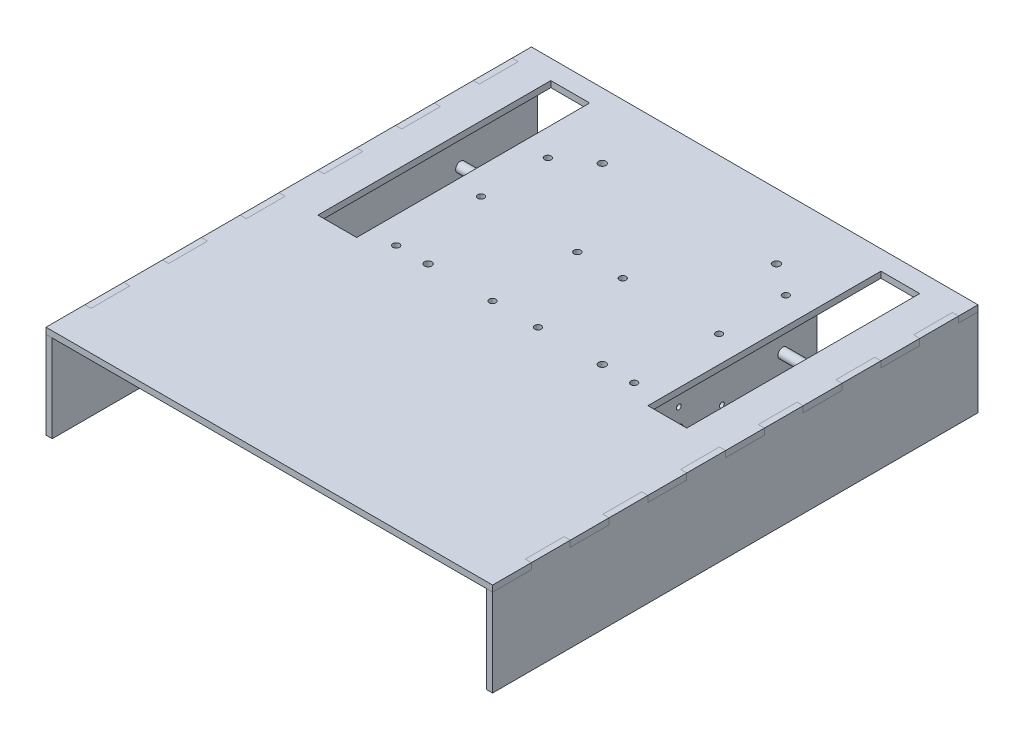
SolidWorks part; units mm, degrees
ref_plane "Front Plane" through (0, 0, 0) normal (0, 0, 1) x (1, 0, 0)
ref_plane "Top Plane" through (0, 0, 0) normal (0, 1, 0) x (1, 0, 0)
ref_plane "Right Plane" through (0, 0, 0) normal (1, 0, 0) x (0, 0, -1)
sketch "Sketch2" plane through (0, 0, 0) normal (0, 1, 0) x (1, 0, 0)
  line L7 (-172.2662, -88.2141) -> (57.7338, -88.2141)
  line L8 (17.7338, 151.7859) -> (37.7338, 151.7859)
  line L9 (57.7338, -88.2141) -> (57.7338, -68.2141)
  line L10 (57.7338, -68.2141) -> (54.5588, -68.2141)
  line L11 (54.5588, -68.2141) -> (54.5588, -48.2141)
  line L12 (54.5588, -48.2141) -> (57.7338, -48.2141)
  line L13 (-172.2662, -88.2141) -> (-172.2662, -68.2141)
  line L14 (-172.2662, -68.2141) -> (-169.0912, -68.2141)
  line L15 (-169.0912, -68.2141) -> (-169.0912, -48.2141)
  line L16 (-169.0912, -48.2141) -> (-172.2662, -48.2141)
  line L17 (-172.2662, -48.2141) -> (-172.2662, -28.2141)
  line L18 (-172.2662, -28.2141) -> (-169.0912, -28.2141)
  line L19 (-169.0912, -28.2141) -> (-169.0912, -8.2141)
  line L20 (-169.0912, -8.2141) -> (-172.2662, -8.2141)
  line L21 (57.7338, -28.2141) -> (54.5588, -28.2141)
  line L22 (54.5588, -28.2141) -> (54.5588, -8.2141)
  line L23 (54.5588, -8.2141) -> (57.7338, -8.2141)
  line L24 (57.7338, -48.2141) -> (57.7338, -28.2141)
  line L25 (-172.2662, -8.2141) -> (-172.2662, 11.7859)
  line L26 (-172.2662, 11.7859) -> (-169.0912, 11.7859)
  line L27 (-169.0912, 11.7859) -> (-169.0912, 31.7859)
  line L28 (-169.0912, 31.7859) -> (-172.2662, 31.7859)
  line L29 (57.7338, 11.7859) -> (54.5588, 11.7859)
  line L30 (54.5588, 11.7859) -> (54.5588, 31.7859)
  line L31 (54.5588, 31.7859) -> (57.7338, 31.7859)
  line L32 (57.7338, -8.2141) -> (57.7338, 11.7859)
  line L33 (-172.2662, 31.7859) -> (-172.2662, 51.7859)
  line L34 (-172.2662, 51.7859) -> (-169.0912, 51.7859)
  line L35 (-169.0912, 51.7859) -> (-169.0912, 71.7859)
  line L36 (-169.0912, 71.7859) -> (-172.2662, 71.7859)
  line L37 (57.7338, 51.7859) -> (54.5588, 51.7859)
  line L38 (54.5588, 51.7859) -> (54.5588, 71.7859)
  line L39 (54.5588, 71.7859) -> (57.7338, 71.7859)
  line L40 (57.7338, 31.7859) -> (57.7338, 51.7859)
  line L45 (17.7338, 151.7859) -> (17.7338, 31.7859)
  line L46 (17.7338, 31.7859) -> (37.7338, 31.7859)
  line L47 (37.7338, 151.7859) -> (37.7338, 31.7859)
  line L48 (-152.2662, 151.7859) -> (-132.2662, 151.7859)
  line L49 (-152.2662, 151.7859) -> (-152.2662, 31.7859)
  line L50 (-152.2662, 31.7859) -> (-132.2662, 31.7859)
  line L51 (-132.2662, 151.7859) -> (-132.2662, 31.7859)
  line L52 (-172.2662, 71.7859) -> (-172.2662, 91.7859)
  line L53 (-172.2662, 91.7859) -> (-169.0912, 91.7859)
  line L54 (-169.0912, 91.7859) -> (-169.0912, 111.7859)
  line L55 (-169.0912, 111.7859) -> (-172.2662, 111.7859)
  line L56 (57.7338, 91.7859) -> (54.5588, 91.7859)
  line L57 (54.5588, 91.7859) -> (54.5588, 111.7859)
  line L58 (54.5588, 111.7859) -> (57.7338, 111.7859)
  line L59 (57.7338, 71.7859) -> (57.7338, 91.7859)
  line L63 (-172.2662, 111.7859) -> (-172.2662, 131.7859)
  line L64 (-172.2662, 131.7859) -> (-169.0912, 131.7859)
  line L65 (-169.0912, 131.7859) -> (-169.0912, 151.7859)
  line L66 (-169.0912, 151.7859) -> (-172.2662, 151.7859)
  line L67 (57.7338, 131.7859) -> (54.5588, 131.7859)
  line L68 (54.5588, 131.7859) -> (54.5588, 151.7859)
  line L69 (54.5588, 151.7859) -> (57.7338, 151.7859)
  line L70 (57.7338, 111.7859) -> (57.7338, 131.7859)
  line L71 (57.7338, 151.7859) -> (57.7338, 161.7859)
  line L72 (57.7338, 161.7859) -> (-172.2662, 161.7859)
  line L73 (-172.2662, 161.7859) -> (-172.2662, 151.7859)
  dimension "D1" = 3.175
  dimension "D2" = 20
  dimension "D3" = 20
  dimension "D4" = 3.175
  dimension "D6" = 230
  dimension "D8" = 20
  dimension "D9" = 20
  dimension "D10" = 20
  dimension "D11" = 20
  dimension "D13" = 120
  dimension "D7" = 10
  dimension "D12" = 10
  dimension "D5" = 6
extrude "Boss-Extrude1" add sketch "Sketch2" along normal blind 3.175
ref_plane "Plane3" through (-57.2662, 0, 0) normal (-1, 0, 0) x (0, 0, 1)
sketch "Sketch3" plane through (-169.0912, 0, 0) normal (-1, 0, 0) x (0, 0, 1)
  line L0 (68.2141, 3.175) -> (68.2141, 0)
  line L1 (68.2141, 0) -> (88.2141, 0)
  line L2 (88.2141, 0) -> (88.2141, -45)
  line L3 (68.2141, 3.175) -> (48.2141, 3.175)
  line L4 (48.2141, 3.175) -> (48.2141, 0)
  line L5 (48.2141, 0) -> (28.2141, 0)
  line L6 (28.2141, 0) -> (28.2141, 3.175)
  line L7 (28.2141, 3.175) -> (8.2141, 3.175)
  line L8 (8.2141, 3.175) -> (8.2141, 0)
  line L9 (8.2141, 0) -> (-11.7859, 0)
  line L10 (-11.7859, 0) -> (-11.7859, 3.175)
  line L11 (-91.7859, 0) -> (-91.7859, 3.175)
  line L12 (-11.7859, 3.175) -> (-31.7859, 3.175)
  line L13 (-31.7859, 3.175) -> (-31.7859, 0)
  line L14 (-31.7859, 0) -> (-51.7859, 0)
  line L15 (-51.7859, 0) -> (-51.7859, 3.175)
  line L16 (-51.7859, 3.175) -> (-71.7859, 3.175)
  line L17 (-71.7859, 3.175) -> (-71.7859, 0)
  line L18 (-71.7859, 0) -> (-91.7859, 0)
  line L21 (-91.7859, 3.175) -> (-111.7859, 3.175)
  line L22 (-111.7859, 3.175) -> (-111.7859, 0)
  line L25 (-111.7859, 0) -> (-131.7859, 0)
  line L26 (-151.7859, 0) -> (-131.7859, 0) construction
  line L27 (-131.7859, 3.175) -> (-131.7859, 0) construction
  line L28 (-131.7859, 0) -> (-131.7859, 3.175)
  line L29 (-131.7859, 3.175) -> (-151.7859, 3.175)
  line L30 (-151.7859, 3.175) -> (-151.7859, 0)
  line L31 (-151.7859, 3.175) -> (-151.7859, 0) construction
  line L32 (-151.7859, 0) -> (-161.732, 0)
  line L33 (-161.732, 0) -> (-161.732, -45)
  line L34 (-161.732, -45) -> (88.2141, -45)
extrude "Boss-Extrude2" add sketch "Sketch3" along normal blind 3.175 separate body
sketch "Sketch4" plane through (0, 0, 0) normal (0, -1, 0) x (1, 0, 0)
  line L0 (-128.2662, -122.8126) -> (-128.2662, -33.5103)
  line L1 (-128.2662, -122.8126) -> (-110.4256, -122.8126)
  line L2 (-128.2662, -33.5103) -> (-110.4287, -33.5103)
  line L5 (-64.765, -32.9867) -> (-64.765, -87.1773)
  line L6 (-64.765, -32.9867) -> (-73.1795, -32.9867)
  line L7 (-64.765, -87.1773) -> (-73.1795, -87.1773)
  line L9 (-110.4287, -33.5103) -> (-110.4287, -55.4044)
  line L10 (-110.4287, -55.4044) -> (-73.1795, -55.4044)
  line L11 (-73.1795, -55.4044) -> (-73.1795, -32.9867)
  line L12 (-73.1795, -87.1773) -> (-73.1795, -65.4044)
  line L13 (-73.1795, -65.4044) -> (-110.4256, -65.4044)
  line L14 (-110.4256, -65.4044) -> (-110.4256, -122.8126)
  point P0 (-110.4287, -34.1968)
extrude "Boss-Extrude3" add sketch "Sketch4" along normal blind 1.6129 separate body
sketch "Sketch6" plane through (-128.2662, 113.8349, 0) normal (1, 0, 0) x (0, -1, 0)
  line L0 (115.4478, 33.5103) -> (113.8349, 33.5103)
  line L1 (113.8349, 33.5103) -> (113.8349, 122.8126)
  line L4 (133.4041, 33.5103) -> (115.4478, 33.5103)
  line L7 (135.755, 122.8126) -> (113.8349, 122.8126)
  line L8 (113.8349, 31.7859) -> (113.8349, 151.7859) construction
  line L10 (115.4478, 122.8126) -> (113.8349, 122.8126) construction
  line L11 (135.755, 122.8126) -> (135.755, 87.3557)
  circle A2 centre (133.4041, 73.86) radius 1.27
  circle A4 centre (133.4041, 51.6858) radius 2.3749
  circle A5 centre (125.8349, 105.2548) radius 2.55
  circle A6 centre (123.1933, 51.6858) radius 1.27
  circle A8 centre (143.6149, 51.6858) radius 1.27
  arc A10 (135.755, 87.3557) -> (133.4041, 33.5103) centre (121.4093, 61.008) cw
  line M25 (113.8349, 33.5103) -> (113.8349, 122.8126)
  line M26 (113.8349, 122.8126) -> (115.4478, 122.8126)
  line M27 (115.4478, 122.8126) -> (115.4478, 33.5103)
  line M28 (115.4478, 33.5103) -> (113.8349, 33.5103)
  dimension "D1" = 5.1
  dimension "D2" = 12
extrude "Boss-Extrude4" add sketch "Sketch6" along normal blind 1.6129 contours M28 M25 M26 M27 | L4 M27 | A6 A2 A4 A8 region at (-128.2662, -15.7988, -73.9814) region at (-128.2662, -0.8065, -78.1615)
sketch "Sketch7" plane through (0, -1.6129, 0) normal (0, -1, 0) x (1, 0, 0)
  circle A0 centre (-118.541, -82.125) radius 1.7
  circle A1 centre (-118.541, -38.4299) radius 1.7
  circle A2 centre (-68.9723, -38.4299) radius 1.7
  circle A3 centre (-68.9723, -82.125) radius 1.7
  circle A4 centre (-118.541, -116.5476) radius 1.7
  circle A5 centre (-102.1184, -38.4299) radius 1.9
  circle A6 centre (-102.1184, -128.1299) radius 1.9
  point P10 (-120.252, -38.4299)
  point P13 (-120.252, -82.125)
  point P14 (-120.252, -116.8459)
  point P17 (0, 0)
  point P18 (-68.9723, -38.4299)
  point P19 (-68.9723, -82.125)
  point P20 (-118.541, -38.4299)
  point P21 (-118.541, -82.125)
  point P22 (-118.541, -116.5476)
  dimension "D3" = 3.4
  dimension "D4" = 3.4
  dimension "D5" = 3.4
  dimension "D6" = 3.4
  dimension "D1" = 3.4
  dimension "D2" = 3.8
  dimension "D8" = 3.8
  dimension "D7" = 89.7
extrude "Cut-Extrude1" cut sketch "Sketch7" against normal blind 10
mirror "Mirror1" about plane through (-57.2662, 0, 0) normal (-1, 0, 0) of bodies 157 103 158
mirror "Mirror2" about plane through (-57.2662, 0, 0) normal (-1, 0, 0) of "Cut-Extrude1"
sketch "Sketch9" plane through (-152.2662, 0, 0) normal (1, 0, 0) x (0, 0, -1)
  circle A0 centre (105.2548, -12) radius 2.5
extrude "Boss-Extrude6" add sketch "Sketch9" along normal blind 189 separate body
equation "\"hardboard_width\"= 3.175"
equation "\"D1@Boss-Extrude1\"=\"hardboard_width\""
equation "\"D1@Sketch2\"=\"hardboard_width\""
equation "\"D4@Sketch2\"=\"hardboard_width\""
equation "\"D1@Boss-Extrude2\"=\"hardboard_width\""
equation "\"steel_24g_thickness\"= 0.5"
equation "\"m3_clearance_hole\"= 3.4"
equation "\"D3@Sketch7\"=\"m3_clearance_hole\""
equation "\"D4@Sketch7\"=\"m3_clearance_hole\""
equation "\"D5@Sketch7\"=\"m3_clearance_hole\""
equation "\"D6@Sketch7\"=\"m3_clearance_hole\""
equation "\"steel_16g_thickness\"=1.6129"
equation "\"D1@Boss-Extrude3\"=\"steel_16g_thickness\""
equation "\"D1@Boss-Extrude4\"=\"steel_16g_thickness\""
equation "\"D1@Sketch7\"=\"m3_clearance_hole\""
